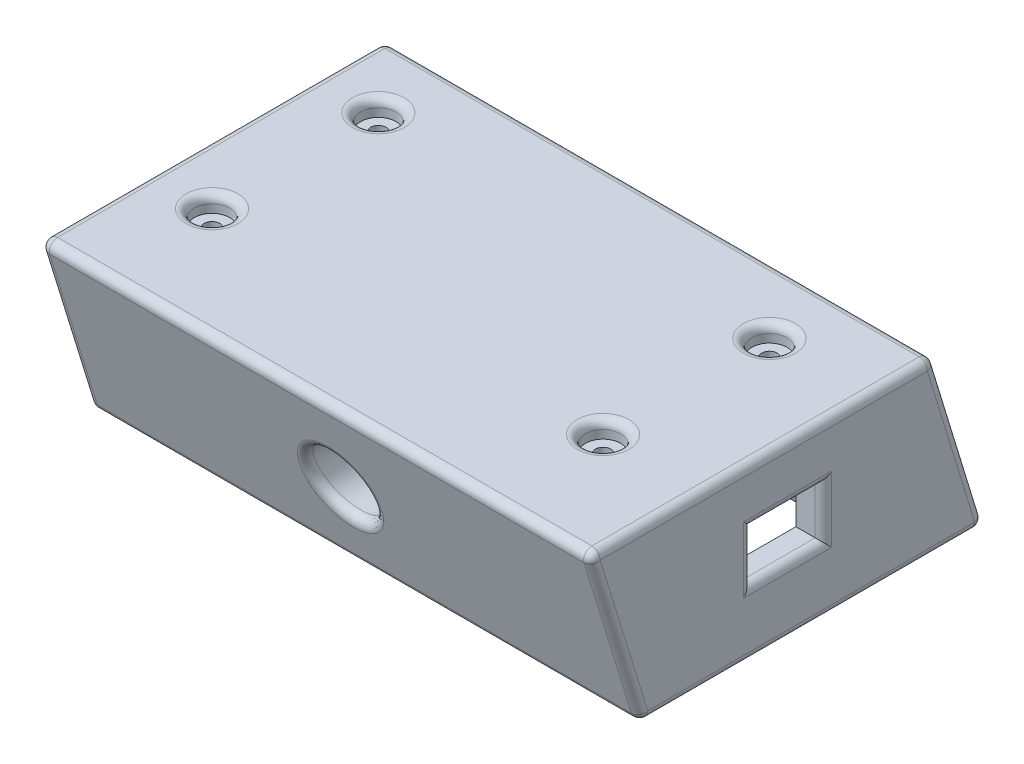
SolidWorks part; units mm, degrees
ref_plane "前基準面" through (0, 0, 0) normal (0, 0, 1) x (1, 0, 0)
ref_plane "上基準面" through (0, 0, 0) normal (0, 1, 0) x (1, 0, 0)
ref_plane "右基準面" through (0, 0, 0) normal (1, 0, 0) x (0, 0, -1)
sketch "草圖1" plane through (0, 0, 0) normal (0, 1, 0) x (1, 0, 0)
  line L1 (0, 0) -> (10, 0)
  line L2 (0, 0) -> (0, 5.3)
  line L3 (0, 5.3) -> (10, 5.3)
  line L4 (10, 0) -> (10, 5.3)
  dimension "D1" = 10
  dimension "D2" = 5.3
extrude "填料-伸長1" add sketch "草圖1" along normal blind 2.8
sketch "草圖3" plane through (0, 0, 0) normal (0, -1, 0) x (1, 0, 0)
  line L1 (9.5, -4.8) -> (0.5, -4.8)
  line L2 (9.5, -4.8) -> (9.5, -0.5)
  line L3 (9.5, -0.5) -> (0.5, -0.5)
  line L4 (0.5, -4.8) -> (0.5, -0.5)
extrude "除料-伸長1" cut sketch "草圖3" against normal blind 2.5
sketch "草圖4" plane through (0, 2.8, 0) normal (0, 1, 0) x (1, 0, 0)
  circle A3 centre (1.1, 1.1) radius 0.14
  circle A4 centre (1.1, 4.12) radius 0.14
  circle A6 centre (8.2, 1.1) radius 0.14
  circle A7 centre (8.2, 4.12) radius 0.14
extrude "除料-伸長2" cut sketch "草圖4" against normal up to surface (0.3 mm away) up to face at (5, 2.5, -2.65)
sketch "草圖5" plane through (10, 0, 0) normal (1, 0, 0) x (0, 0, -1)
  line L1 (3.3, 2.1) -> (2, 2.1)
  line L2 (3.3, 2.1) -> (3.3, 1.2)
  line L3 (3.3, 1.2) -> (2, 1.2)
  line L4 (2, 2.1) -> (2, 1.2)
  dimension "D1" = 0.9
  dimension "D2" = 1.3
extrude "除料-伸長3" cut sketch "草圖5" against normal up to next
sketch "草圖7" plane through (0, 0, -5.3) normal (0, 0, -1) x (-1, 0, 0)
  line L1 (-8, 0.3) -> (-5, 0.3)
  line L2 (-8, 0.3) -> (-8, 0.8)
  line L3 (-8, 0.8) -> (-5, 0.8)
  line L4 (-5, 0.3) -> (-5, 0.8)
extrude "除料-伸長4" cut sketch "草圖7" against normal up to next and the other way blind 10 contours L2 L1 L4 L3
sketch "草圖8" plane through (0, 2.8, 0) normal (0, 1, 0) x (1, 0, 0)
  line L1 (10, 0) -> (0, 0)
  line L2 (10, 0) -> (10, 5.3)
  line L3 (10, 5.3) -> (0, 5.3)
  line L4 (0, 0) -> (0, 5.3)
  circle A0 centre (8.2, 1.1) radius 0.32
  circle A1 centre (8.2, 4.12) radius 0.32
  circle A2 centre (1.1, 4.12) radius 0.32
  circle A3 centre (1.1, 1.1) radius 0.32
extrude "填料-伸長4" add sketch "草圖8" along normal blind 0.3
sketch "草圖9" plane through (0, 0, 0) normal (-1, 0, 0) x (0, 0, 1)
  line L0 (-5.3, 0) -> (-6.2489, 0)
  line L1 (-6.2489, 0) -> (-5.3, 3.1)
  line L2 (-5.3, 3.1) -> (-5.3, 0)
extrude "填料-伸長5" add sketch "草圖9" against normal up to surface (10 mm away) up to face at (10, 1.65, -2.65)
sketch "草圖10" plane through (0, 0, -4.8) normal (0, 0, 1) x (1, 0, 0)
  line L1 (5, 0.8) -> (8, 0.8)
  line L2 (5, 0.8) -> (5, 0.3)
  line L3 (5, 0.3) -> (8, 0.3)
  line L4 (8, 0.8) -> (8, 0.3)
extrude "除料-伸長5" cut sketch "草圖10" against normal up to next
sketch "草圖11" plane through (0, 0, 0) normal (0, 0, 1) x (1, 0, 0)
  circle A0 centre (5.4, 1.7) radius 0.6
  point P2 (0, 0)
  point P3 (0, 0)
scale "縮放比例1" bodies to scale 112 scale about centroid uniform scaling yes scale factor 10
sketch "草圖13" plane through (55.6242, 0, 0) normal (1, 0, 0) x (0, 0, -1)
sketch "草圖14" plane through (55.6242, 0, 0) normal (1, 0, 0) x (0, 0, -1)
  line L0 (-28.1954, -16.5239) -> (-28.1954, 14.4761)
  line L1 (-28.1954, 14.4761) -> (-37.7616, 14.4761)
  line L2 (-37.7616, 14.4761) -> (-28.1954, -16.5239)
extrude "填料-伸長7" add sketch "草圖14" against normal up to surface (100 mm away) contours L2 L0 L1 up to face at (-44.3758, -1.0239, -0.6768)
sketch "草圖15" plane through (0, 0, 23.1954) normal (0, 0, -1) x (-1, 0, 0)
  circle A0 centre (-5.4, -1.7) radius 6
extrude "除料-伸長6" cut sketch "草圖15" against normal up to surface (9.5745 mm away) up to face at (5.6242, -1.0239, 32.9785)
fillet "圓角3" radius 1.5 40 edges at (50.6242, -16.5239, 1.6954) (-39.3758, -16.5239, 1.6954) (-39.3758, -4.0239, -19.8046) (5.6242, 8.4761, -19.8046) (50.6242, -4.0239, -19.8046) (5.6242, -16.5239, -19.8046) (20.6242, -13.5239, -19.8046) (35.6242, -11.0239, -19.8046) (20.6242, -8.5239, -19.8046) (5.6242, -11.0239, -19.8046) (50.6242, -4.0239, 23.1954) (5.6242, 8.4761, 23.1954) (-39.3758, -4.0239, 23.1954) (5.6242, -16.5239, 23.1954) (-0.6, -1.7, 23.1954) (5.6242, 14.4761, -24.8046) (5.6242, -16.5239, -34.2932) (20.6242, -8.5239, -31.8445) (35.6242, -11.0239, -32.6097) (20.6242, -13.5239, -33.3749) (5.6242, -11.0239, -32.6097) (55.6242, 14.4761, 6.4785) (55.6242, -1.0239, -29.5489) (55.6242, -16.5239, -3.0489) (55.6242, -0.0239, 8.1954) (55.6242, -4.5239, 1.6954) (55.6242, -0.0239, -4.8046) (55.6242, 4.4761, 1.6954) (-44.3758, -1.0239, -29.5489) (-44.3758, 14.4761, 6.4785) (-44.3758, -16.5239, -3.0489) (5.6242, 14.4761, 37.7616) (55.6242, -1.0239, 32.9785) (5.6242, -16.5239, 28.1954) (-44.3758, -1.0239, 32.9785) (5.4, -7.7, 30.9183) (-33.3758, 14.4761, 20.3954) (-33.3758, 14.4761, -9.8046) (37.6242, 14.4761, -9.8046) (37.6242, 14.4761, 20.3954)
